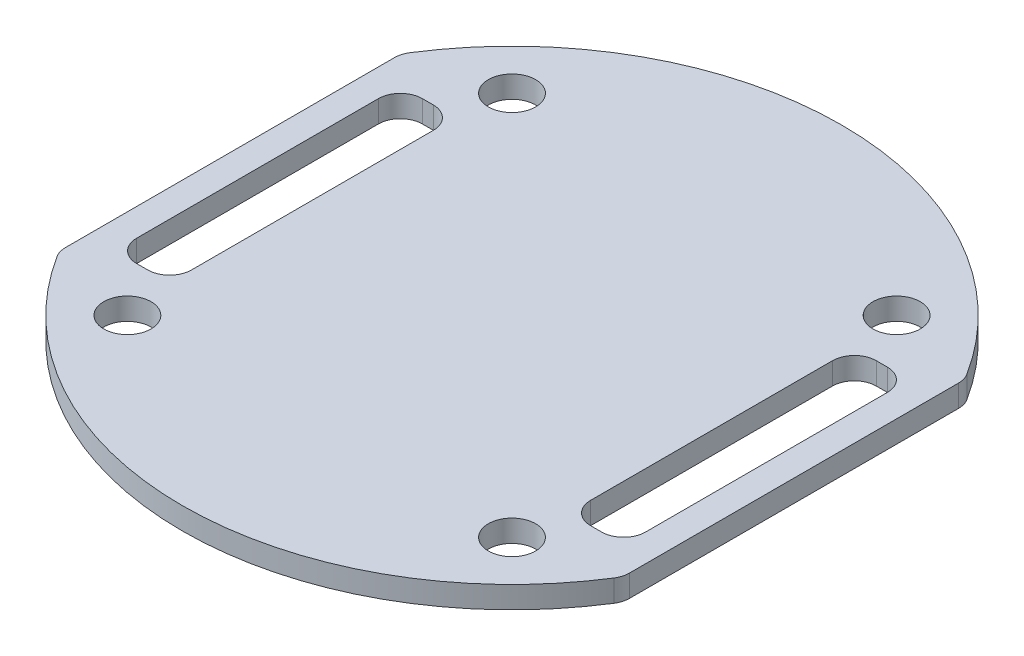
SolidWorks part; units mm, degrees
material "Acrylic (Medium-high impact)"
ref_plane "Front Plane" through (0, 0, 0) normal (0, 0, 1) x (1, 0, 0)
ref_plane "Top Plane" through (0, 0, 0) normal (0, 1, 0) x (1, 0, 0)
ref_plane "Right Plane" through (0, 0, 0) normal (1, 0, 0) x (0, 0, -1)
ref_axis "x-axis" through (88.99, 0, 0) along (-1, 0, 0)
ref_axis "y-axis" through (0, 0, 55) along (0, 0, -1)
ref_axis "z-axis" through (0, 55, 0) along (0, -1, 0)
sketch "Sketch2" plane through (0, 0, 0) normal (0, 1, 0) x (1, 0, 0)
  circle A0 centre (0, 0) radius 30
  dimension "D1" = 60
extrude "AcrylicBase" add sketch "Sketch2" along normal mid plane 2
sketch "Sketch3" plane through (0, 1, 0) normal (0, 1, 0) x (1, 0, 0)
  line L0 (0, 30) -> (0, -30) construction
  line L1 (-23.1571, 13) -> (-18.1571, 13)
  line L2 (-23.1571, 13) -> (-23.1571, -13)
  line L3 (-23.1571, -13) -> (-18.1571, -13)
  line L4 (-18.1571, 13) -> (-18.1571, -13)
  line L5 (-23.1571, 13) -> (-18.1571, -13) construction
  line L6 (-18.1571, 13) -> (-23.1571, -13) construction
  line L7 (0, 0) -> (-20.6571, 0) construction
  line L8 (23.1571, -13) -> (18.1571, -13)
  line L9 (23.1571, 13) -> (23.1571, -13)
  line L10 (23.1571, 13) -> (18.1571, 13)
  line L11 (18.1571, 13) -> (18.1571, -13)
  circle A0 centre (0, 0) radius 30 construction
  dimension "D1" = 5
  dimension "D2" = 26
  dimension "D3" = 20.6571
extrude "wheels" cut sketch "Sketch3" against normal through all
sketch "Sketch4" plane through (0, 1, 0) normal (0, 1, 0) x (1, 0, 0)
  circle A0 centre (-17.5, 17.5) radius 2.1526 construction
  circle A1 centre (-17.5, -17.5) radius 2.1526 construction
  circle A2 centre (17.5, -17.5) radius 2.1526 construction
  circle A3 centre (17.5, 17.5) radius 2.1526 construction
  circle A4 centre (-17.5, 17.5) radius 2.1527
  circle A5 centre (-17.5, -17.5) radius 2.1527
  circle A6 centre (17.5, -17.5) radius 2.1526
  circle A7 centre (17.5, 17.5) radius 2.1526
extrude "holes" cut sketch "Sketch4" against normal through all
sketch "Sketch5" plane through (0, 1, 0) normal (0, 1, 0) x (1, 0, 0)
  line L0 (-25.6571, -15.5471) -> (-25.6571, 15.5471)
  line L1 (25.6571, -15.5471) -> (25.6571, 15.5471)
  line L3 (-23.1571, 13) -> (-23.1571, -13) construction
  circle A0 centre (0, 0) radius 30 construction
  circle A1 centre (0, 0) radius 30
  circle A3 centre (0, 0) radius 30
  circle A4 centre (0, 0) radius 30
  dimension "D2" = 2.5
  dimension "D1" = 0
extrude "flatSides" cut sketch "Sketch5" against normal through all contours L0 | L1 region at (-27.4055, 1, 0) region at (27.4055, 1, 0)
fillet "reliefs" radius 2 12 edges at (18.1571, 0, -13) (23.1571, 0, -13) (23.1571, 0, 13) (18.1571, 0, 13) (-23.1571, 0, 13) (-18.1571, 0, 13) (-18.1571, 0, -13) (-23.1571, 0, -13) (25.6571, 0, -15.5471) (25.6571, 0, 15.5471) (-25.6571, 0, 15.5471) (-25.6571, 0, -15.5471)
